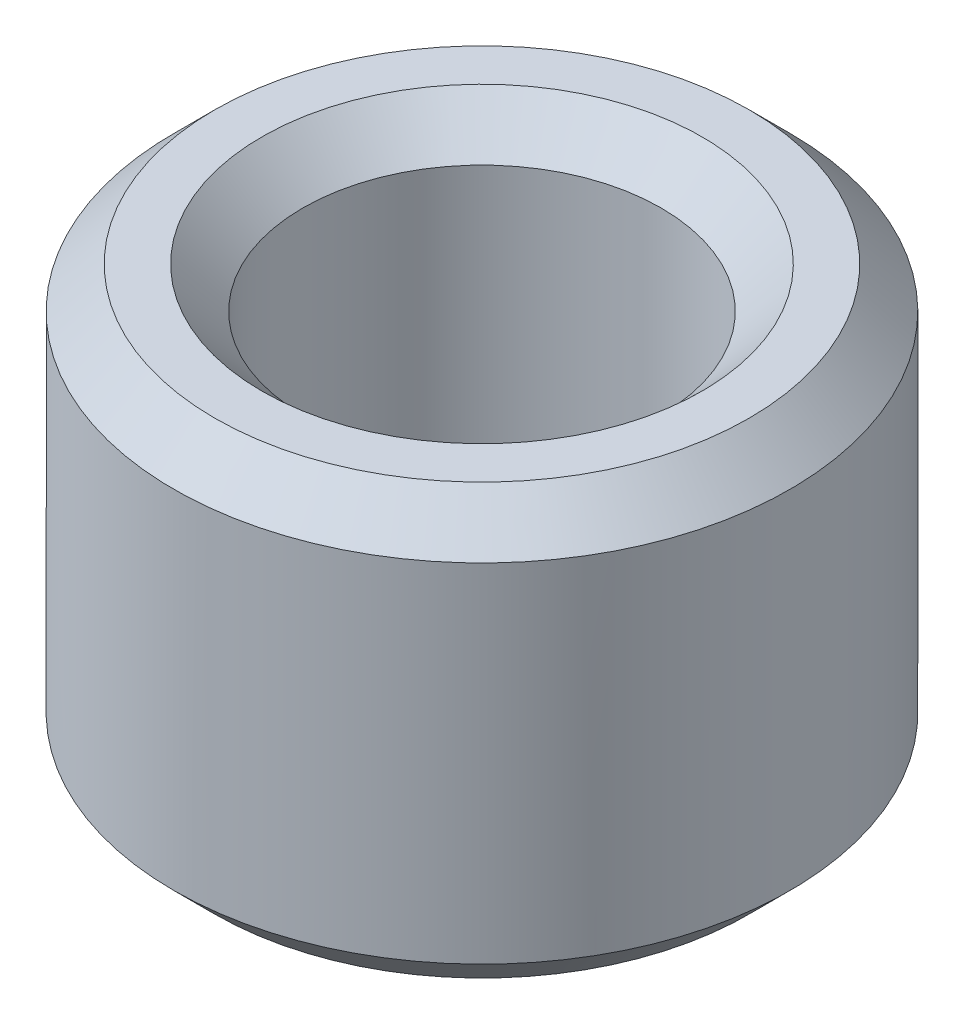
SolidWorks part; units mm, degrees
ref_plane "Front Plane" through (0, 0, 0) normal (0, 0, 1) x (1, 0, 0)
ref_plane "Top Plane" through (0, 0, 0) normal (0, 1, 0) x (1, 0, 0)
ref_plane "Right Plane" through (0, 0, 0) normal (1, 0, 0) x (0, 0, -1)
sketch "Sketch1" plane through (0, 0, 0) normal (0, 1, 0) x (1, 0, 0)
  circle A0 centre (0, 0) radius 20
  dimension "SLEEVE_OD" = 40
extrude "Boss-Extrude1" add sketch "Sketch1" along normal blind 27.8747
sketch "Sketch2" plane through (0, 0, 0) normal (0, 1, 0) x (1, 0, 0)
  circle A0 centre (0, 0) radius 11.626
  dimension "BORE_D" = 23.2521
extrude "Cut-Extrude1" cut sketch "Sketch2" along normal through all
chamfer "Chamfer1" distance 2.6623 angle 45 4 edges at (0, 27.8747, 11.626) (0, 0, 11.626) (0, 0, 20) (0, 27.8747, 20)
